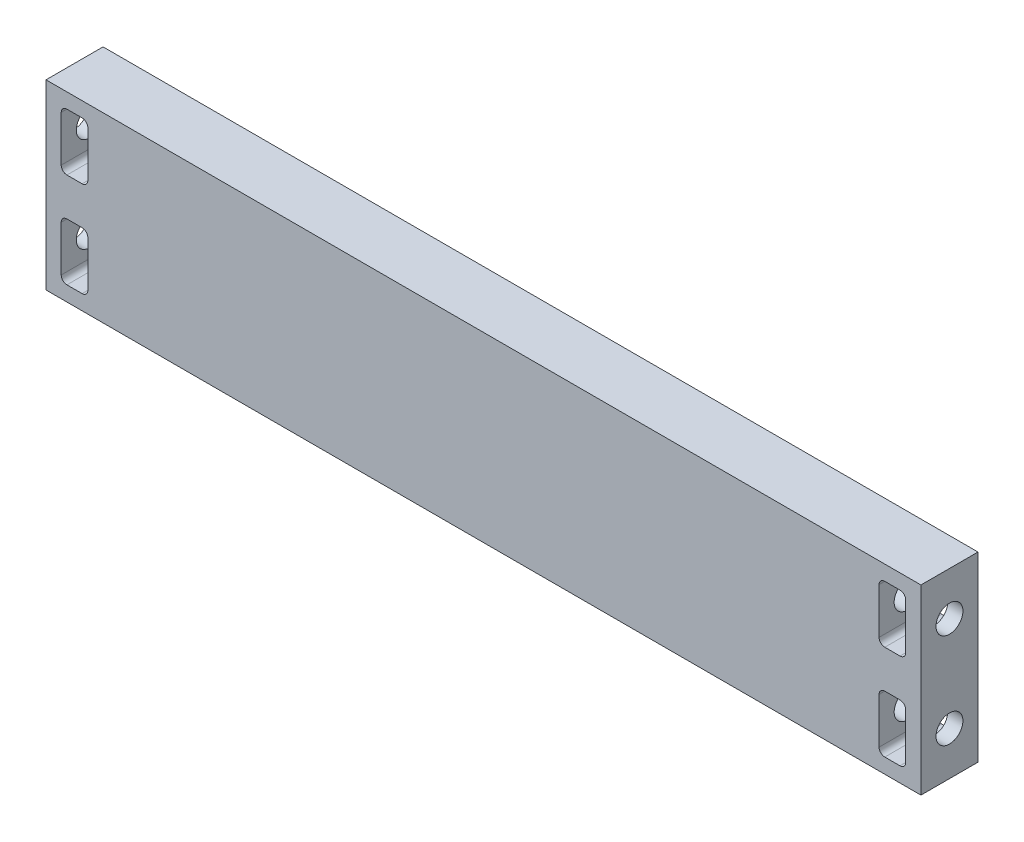
SolidWorks part; units mm, degrees
material "PE High Density"
ref_plane "Front Plane" through (0, 0, 0) normal (0, 0, 1) x (1, 0, 0)
ref_plane "Top Plane" through (0, 0, 0) normal (0, 1, 0) x (1, 0, 0)
ref_plane "Right Plane" through (0, 0, 0) normal (1, 0, 0) x (0, 0, -1)
sketch "Sketch1" plane through (0, 0, 0) normal (0, 0, 1) x (1, 0, 0)
  line L0 (-69.5325, 12.7) -> (-66.9925, 12.7)
  line L1 (-73.025, 15.1929) -> (73.025, 15.1929)
  line L2 (-73.025, 15.1929) -> (-73.025, -15.1929)
  line L3 (-73.025, -15.1929) -> (73.025, -15.1929)
  line L4 (73.025, 15.1929) -> (73.025, -15.1929)
  line L5 (-73.025, 15.1929) -> (73.025, -15.1929) construction
  line L6 (-73.025, -15.1929) -> (73.025, 15.1929) construction
  line L7 (-70.485, 11.7475) -> (-70.485, 4.1275)
  line L8 (-69.5325, 3.175) -> (-66.9925, 3.175)
  line L9 (-66.04, 11.7475) -> (-66.04, 4.1275)
  line L10 (-70.485, 12.7) -> (-66.04, 3.175) construction
  line L11 (-70.485, 3.175) -> (-66.04, 12.7) construction
  line L12 (-68.2625, 15.875) -> (-68.2625, -15.875) construction
  line L13 (-68.2625, 3.175) -> (-68.2625, 11.967) construction
  line L14 (-70.485, 7.9375) -> (-66.04, 7.9375) construction
  line L15 (-73.025, 0) -> (73.025, 0) construction
  line L16 (0, -15.1929) -> (0, 15.1929) construction
  line L17 (-70.485, -7.9375) -> (-66.04, -7.9375) construction
  line L18 (-68.2625, -3.175) -> (-68.2625, -11.967) construction
  line L19 (-70.485, -3.175) -> (-66.04, -12.7) construction
  line L20 (-70.485, -12.7) -> (-66.04, -3.175) construction
  line L21 (-66.04, -11.7475) -> (-66.04, -4.1275)
  line L22 (-69.5325, -3.175) -> (-66.9925, -3.175)
  line L23 (-70.485, -11.7475) -> (-70.485, -4.1275)
  line L24 (-69.5325, -12.7) -> (-66.9925, -12.7)
  line L25 (70.485, 7.9375) -> (66.04, 7.9375) construction
  line L26 (68.2625, 3.175) -> (68.2625, 11.967) construction
  line L27 (70.485, 3.175) -> (66.04, 12.7) construction
  line L28 (70.485, 12.7) -> (66.04, 3.175) construction
  line L29 (66.04, 11.7475) -> (66.04, 4.1275)
  line L30 (69.5325, 3.175) -> (66.9925, 3.175)
  line L31 (70.485, 11.7475) -> (70.485, 4.1275)
  line L32 (69.5325, 12.7) -> (66.9925, 12.7)
  line L33 (70.485, -12.7) -> (66.04, -3.175) construction
  line L34 (70.485, -3.175) -> (66.04, -12.7) construction
  line L35 (68.2625, -3.175) -> (68.2625, -11.967) construction
  line L36 (70.485, -7.9375) -> (66.04, -7.9375) construction
  line L37 (69.5325, -12.7) -> (66.9925, -12.7)
  line L38 (70.485, -11.7475) -> (70.485, -4.1275)
  line L39 (69.5325, -3.175) -> (66.9925, -3.175)
  line L40 (66.04, -11.7475) -> (66.04, -4.1275)
  arc A0 (-66.9925, 3.175) -> (-66.04, 4.1275) centre (-66.9925, 4.1275) ccw
  arc A1 (-66.9925, 12.7) -> (-66.04, 11.7475) centre (-66.9925, 11.7475) cw
  arc A2 (-69.5325, 3.175) -> (-70.485, 4.1275) centre (-69.5325, 4.1275) cw
  arc A3 (-69.5325, 12.7) -> (-70.485, 11.7475) centre (-69.5325, 11.7475) ccw
  arc A4 (-69.5325, -12.7) -> (-70.485, -11.7475) centre (-69.5325, -11.7475) cw
  arc A5 (-69.5325, -3.175) -> (-70.485, -4.1275) centre (-69.5325, -4.1275) ccw
  arc A6 (-66.9925, -12.7) -> (-66.04, -11.7475) centre (-66.9925, -11.7475) ccw
  arc A7 (-66.9925, -3.175) -> (-66.04, -4.1275) centre (-66.9925, -4.1275) cw
  arc A8 (69.5325, 12.7) -> (70.485, 11.7475) centre (69.5325, 11.7475) cw
  arc A9 (69.5325, 3.175) -> (70.485, 4.1275) centre (69.5325, 4.1275) ccw
  arc A10 (66.9925, 12.7) -> (66.04, 11.7475) centre (66.9925, 11.7475) ccw
  arc A11 (66.9925, 3.175) -> (66.04, 4.1275) centre (66.9925, 4.1275) cw
  arc A12 (66.9925, -3.175) -> (66.04, -4.1275) centre (66.9925, -4.1275) ccw
  arc A13 (66.9925, -12.7) -> (66.04, -11.7475) centre (66.9925, -11.7475) cw
  arc A14 (69.5325, -3.175) -> (70.485, -4.1275) centre (69.5325, -4.1275) cw
  arc A15 (69.5325, -12.7) -> (70.485, -11.7475) centre (69.5325, -11.7475) ccw
  point P0 (0, 0)
  point P6 (-68.2625, 7.9375)
  point P53 (-68.2625, -7.9375)
  point P74 (68.2625, 7.9375)
  point P95 (68.2625, -7.9375)
  dimension "D5" = 0.9525
  dimension "D6" = 0.9525
  dimension "D7" = 0.9525
  dimension "D8" = 0.9525
  dimension "D1" = 146.05
  dimension "D2" = 30.3858
  dimension "D3" = 4.445
  dimension "D4" = 9.525
  dimension "D9" = 4.7625
  dimension "D10" = 7.9375
extrude "Boss-Extrude1" add sketch "Sketch1" along normal blind 9.525
sketch "Sketch2" plane through (73.025, 0, 0) normal (1, 0, 0) x (0, 0, -1)
  line L0 (-4.7625, 15.1929) -> (-4.7625, -15.1929) construction
  line L1 (-9.525, 15.1929) -> (0, 15.1929) construction
  line L2 (-9.525, -15.1929) -> (0, -15.1929) construction
  line L3 (-9.525, 0) -> (0, 0) construction
  line L4 (-9.525, -15.1929) -> (-9.525, 15.1929) construction
  circle A0 centre (-4.7625, 7.9375) radius 2.2479
  dimension "D1" = 4.4958
  dimension "D2" = 7.9375
extrude "Cut-Extrude1" cut sketch "Sketch2" against normal blind 10.795
mirror "Mirror1" about plane through (0, 0, 0) normal (1, 0, 0) of "Cut-Extrude1" second plane through (0, 0, 0) second plane normal (0, 1, 0)
equation "\"Plate Width\" = 4.6in"
equation "\"Plate Thickness\" = 0.375in"
equation "\"Num holes\" = 4"
equation "\"Plate Height\" = 1.25in"
equation "\"Top Plate Width\" = 4.5in"
equation "\"Plate Clearance Hole Diameter\" = 0.125in"
equation "\"Plate Tap Hole Diameter\" = 0.116in"
equation "\"Bottom Plate Length\" = 6.5in"
equation "\"Number Eight Clearance Size\" = 0.177in"
equation "\"D1@Sketch1\"=\"Bottom Plate Length\" - \"Plate Thickness\" * 2"
equation "\"D2@Sketch1\"=\"Back Brace Height\""
equation "\"D9@Sketch1\"=\"Plate Thickness\"/2"
equation "\"D10@Sketch1\"=\"Plate Height\"/4"
equation "\"D1@Boss-Extrude1\"=\"Plate Thickness\""
equation "\"D1@Sketch2\"=\"Number Eight Clearance Size\""
equation "\"D2@Sketch2\"=\"Plate Height\"/4"
equation "\"D1@Cut-Extrude1\"=0.8 - \"Plate Thickness\""
equation "\"Back Brace Height\" = 1.1962912in"
